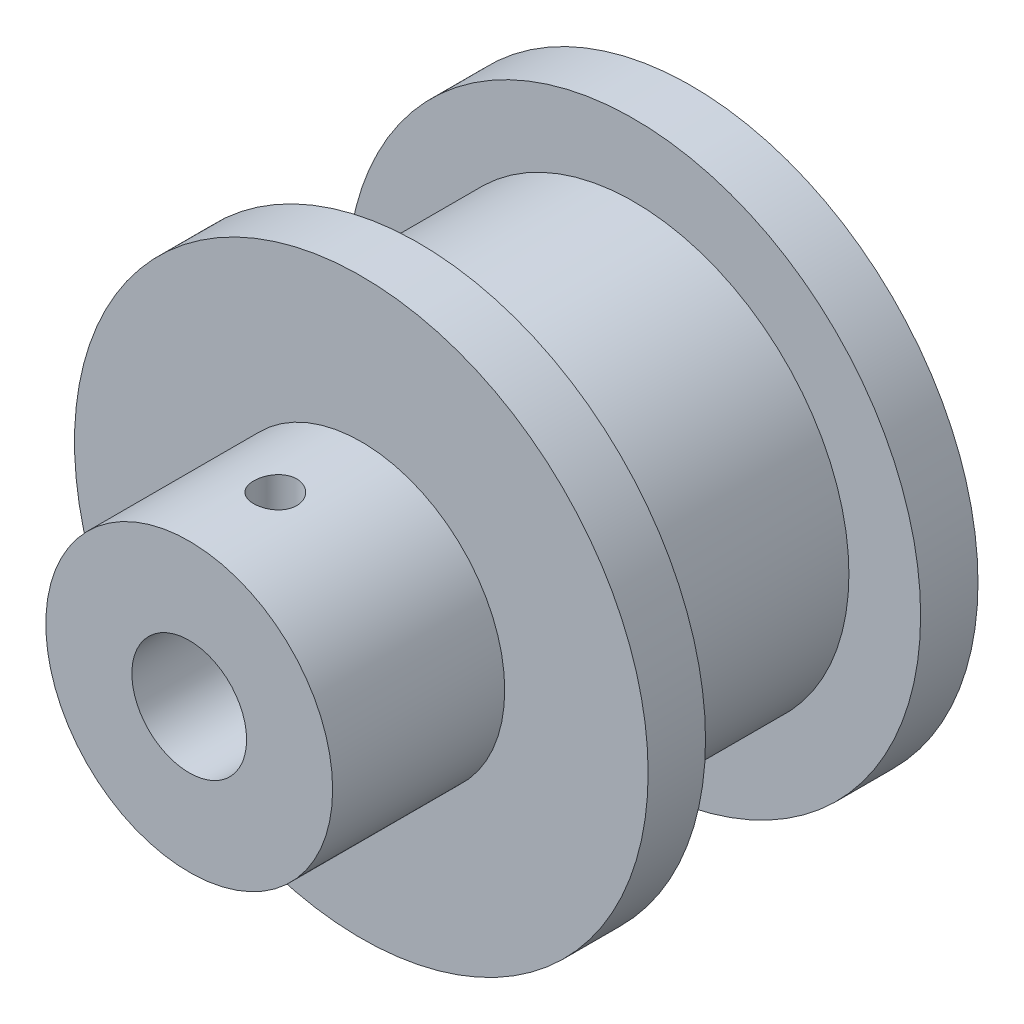
SolidWorks part; units mm, degrees
ref_plane "정면" through (0, 0, 0) normal (0, 0, 1) x (1, 0, 0)
ref_plane "윗면" through (0, 0, 0) normal (0, 1, 0) x (1, 0, 0)
ref_plane "우측면" through (0, 0, 0) normal (1, 0, 0) x (0, 0, -1)
sketch "스케치1" plane through (0, 0, 0) normal (0, 0, 1) x (1, 0, 0)
  circle A0 centre (0, 0) radius 20
  circle A1 centre (0, 0) radius 15
  dimension "D1" = 40
  dimension "D2" = 30
extrude "보스-돌출1" add sketch "스케치1" against normal blind 4 contours A1 | A0 A1 region at (-19.4343, 0, 0) region at (0, 0, 0)
extrude "보스-돌출2" add sketch "스케치1<3>" along normal blind 15 contours A1 region at (0, 0, 0)
sketch "스케치1<3>" plane through (0, 0, 0) normal (0, 0, 1) x (1, 0, 0) same geometry as "스케치1"
sketch "스케치2" plane through (0, 0, 15) normal (0, 0, 1) x (1, 0, 0)
  circle A0 centre (0, 0) radius 20
  dimension "D1" = 40
extrude "보스-돌출3" add sketch "스케치2" along normal blind 4
sketch "스케치3" plane through (0, 0, 19) normal (0, 0, 1) x (1, 0, 0)
  circle A0 centre (0, 0) radius 10
  circle A1 centre (0, 0) radius 4
  circle A2 centre (0, 0) radius 20
  circle A3 centre (0, 0) radius 20
  dimension "D1" = 20
  dimension "D2" = 0
  dimension "D3" = 8
extrude "보스-돌출4" add sketch "스케치3" along normal blind 12 contours A0 region at (-9.7172, 0, 19)
sketch "스케치4" plane through (0, 0, 0) normal (0, 1, 0) x (1, 0, 0)
  line L0 (10, -19) -> (10, -31)
  line L1 (-10, -31) -> (-10, -19)
  line L2 (-10, -31) -> (-10, -19)
  line L3 (10, -19) -> (10, -31)
  line L4 (4, -19) -> (4, -31)
  line L5 (-4, -31) -> (-4, -19)
  line L6 (-4, -31) -> (-4, -19)
  line L7 (4, -19) -> (4, -31)
  line L8 (4, -25) -> (-4, -25) construction
  circle A0 centre (0, -25) radius 1.5
  dimension "D1" = 3
extrude "컷-돌출1" cut sketch "스케치4" along normal blind 18 contours A0 L8 | L8 A0 region at (0, 0, 25.6366) region at (0, 0, 24.3634)
extrude "컷-돌출2" cut sketch "스케치3<3>" against normal blind 27 contours A1 region at (0, 0, 19)
sketch "스케치3<3>" plane through (0, 0, 19) normal (0, 0, 1) x (1, 0, 0) same geometry as "스케치3"
